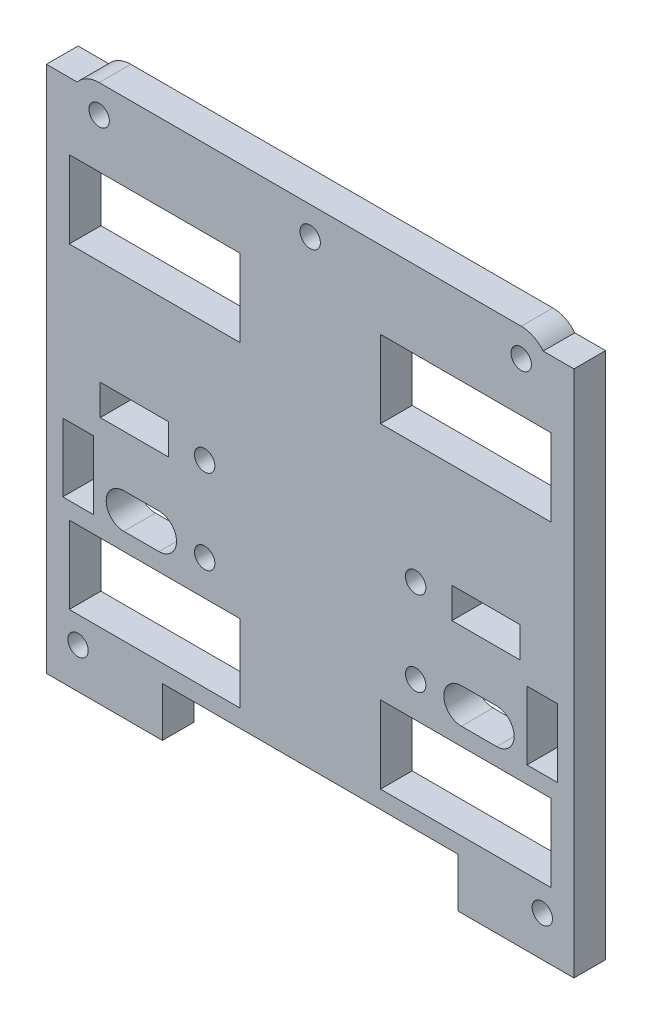
SolidWorks part; units mm, degrees
ref_plane "Front Plane" through (0, 0, 0) normal (0, 0, 1) x (1, 0, 0)
ref_plane "Top Plane" through (0, 0, 0) normal (0, 1, 0) x (1, 0, 0)
ref_plane "Right Plane" through (0, 0, 0) normal (1, 0, 0) x (0, 0, -1)
sketch "Sketch1" plane through (0, 0, 0) normal (0, 0, 1) x (1, 0, 0)
  line L0 (0, -37.5) -> (0, 37.5) construction
  line L1 (-47.5, -37.5) -> (47.5, -37.5)
  line L2 (-47.5, -37.5) -> (-47.5, 37.5)
  line L3 (-47.5, 37.5) -> (47.5, 37.5)
  line L4 (47.5, -37.5) -> (47.5, 37.5)
  line L5 (-47.5, -37.5) -> (47.5, 37.5) construction
  line L6 (-47.5, 37.5) -> (47.5, -37.5) construction
  line L7 (-47.5, 0) -> (47.5, 0) construction
  line L8 (-47.5, 22.5) -> (47.5, 22.5) construction
  line L9 (34.25, 17) -> (10, 28) construction
  line L10 (-34.25, 28) -> (-10, 28)
  line L11 (-34.25, 28) -> (-34.25, 17)
  line L12 (-34.25, 17) -> (-10, 17)
  line L13 (-10, 28) -> (-10, 17)
  line L14 (-34.25, 28) -> (-10, 17) construction
  line L15 (-34.25, 17) -> (-10, 28) construction
  line L16 (34.25, 28) -> (10, 17) construction
  line L17 (10, 28) -> (10, 17)
  line L18 (34.25, 17) -> (10, 17)
  line L19 (34.25, 28) -> (34.25, 17)
  line L20 (34.25, 28) -> (10, 28)
  line L21 (34.25, -28) -> (10, -17) construction
  line L22 (-34.25, -17) -> (-10, -28) construction
  line L23 (-34.25, -28) -> (-10, -17) construction
  line L24 (34.25, -17) -> (10, -28) construction
  line L25 (34.25, -28) -> (10, -28)
  line L26 (34.25, -28) -> (34.25, -17)
  line L27 (34.25, -17) -> (10, -17)
  line L28 (10, -28) -> (10, -17)
  line L29 (-10, -28) -> (-10, -17)
  line L30 (-34.25, -17) -> (-10, -17)
  line L31 (-34.25, -28) -> (-34.25, -17)
  line L32 (-34.25, -28) -> (-10, -28)
  point P0 (0, 0)
  point P12 (-22.125, 22.5)
  point P21 (22.125, 22.5)
  point P30 (22.125, -22.5)
  point P31 (-22.125, -22.5)
  dimension "D1" = 95
  dimension "D2" = 75
  dimension "D3" = 22.5
  dimension "D4" = 24.25
  dimension "D5" = 11
  dimension "D6" = 10
extrude "Boss-Extrude1" add sketch "Sketch1" along normal blind 4.5
sketch "Sketch8" plane through (0, 0, 4.5) normal (0, 0, 1) x (1, 0, 0)
  line L0 (-47.5, 37.5) -> (-47.5, -37.5) construction
  line L1 (47.5, -37.5) -> (47.5, 37.5) construction
  circle A0 centre (-47.5, 29.5) radius 8
  circle A1 centre (47.5, 29.5) radius 8
  dimension "D1" = 16
extrude "Boss-Extrude2" [suppressed] add sketch "Sketch8" against normal through all
sketch "Sketch2" plane through (0, 0, 4.5) normal (0, 0, 1) x (1, 0, 0)
  line L0 (0, -37.5) -> (0, 37.5) construction
  line L1 (-47.5, -37.5) -> (47.5, -37.5) construction
  line L2 (47.5, 37.5) -> (-47.5, 37.5) construction
  line L3 (-47.5, 0) -> (47.5, 0) construction
  line L4 (-47.5, 37.5) -> (-47.5, -37.5) construction
  line L5 (47.5, -37.5) -> (47.5, 37.5) construction
  line L6 (-40, 0) -> (40, 0) construction
  line L7 (-30, 35) -> (30, 35) construction
  circle A0 centre (-30, 35) radius 1.45
  circle A1 centre (30, 35) radius 1.45
  circle A2 centre (40, 0) radius 1.45
  circle A3 centre (-40, 0) radius 1.45
  circle A4 centre (0, 35) radius 1.45
  dimension "D1" = 2.9
  dimension "D7" = 2.9
  dimension "D8" = 2.9
  dimension "D9" = 2.9
  dimension "D2" = 30
  dimension "D3" = 35
  dimension "D4" = 80
  dimension "D5" = 40
  dimension "D6" = 0
extrude "screwHoles" cut sketch "Sketch2" against normal through all
sketch "Sketch3" plane through (0, 0, 4.5) normal (0, 0, 1) x (1, 0, 0)
  line L0 (-47.5, -20) -> (26.0486, -20) construction
  line L1 (-47.5, 37.5) -> (-47.5, -37.5) construction
  line L3 (0, 37.5) -> (0, -37.5) construction
  line L4 (47.5, 37.5) -> (-47.5, 37.5) construction
  line L5 (-47.5, -37.5) -> (47.5, -37.5) construction
  line L6 (18.95, -22.2) -> (9.05, -17.8) construction
  line L7 (-18.95, -17.8) -> (-9.05, -17.8)
  line L8 (-18.95, -17.8) -> (-18.95, -22.2)
  line L9 (-18.95, -22.2) -> (-9.05, -22.2)
  line L10 (-9.05, -17.8) -> (-9.05, -22.2)
  line L11 (-18.95, -17.8) -> (-9.05, -22.2) construction
  line L12 (-18.95, -22.2) -> (-9.05, -17.8) construction
  line L13 (18.95, -17.8) -> (9.05, -22.2) construction
  line L14 (9.05, -17.8) -> (9.05, -22.2)
  line L15 (18.95, -22.2) -> (9.05, -22.2)
  line L16 (18.95, -17.8) -> (18.95, -22.2)
  line L17 (18.95, -17.8) -> (9.05, -17.8)
  line L18 (-47.5, 37.5) -> (-47.5, -37.5) construction
  point P2 (-47.5, 0)
  point P12 (-14, -20)
  point P21 (14, -20)
  dimension "D1" = 9.9
  dimension "D3" = 14
  dimension "D4" = 20
extrude "BeltClamp" [suppressed] cut sketch "Sketch3" against normal through all
sketch "Sketch4" plane through (0, 0, 4.5) normal (0, 0, 1) x (1, 0, 0)
  line L0 (-47.5, 0) -> (47.5, 0) construction
  line L1 (-47.5, 37.5) -> (-47.5, -37.5) construction
  line L2 (47.5, -37.5) -> (47.5, 37.5) construction
  line L3 (0, 0) -> (0, 33.55) construction
  line L4 (-29.85, 2.175) -> (-20.15, 2.175)
  line L5 (-29.85, 2.175) -> (-29.85, -2.175)
  line L6 (-29.85, -2.175) -> (-20.15, -2.175)
  line L7 (-20.15, 2.175) -> (-20.15, -2.175)
  line L8 (-29.85, 2.175) -> (-20.15, -2.175) construction
  line L9 (-29.85, -2.175) -> (-20.15, 2.175) construction
  line L10 (29.85, -2.175) -> (20.15, 2.175) construction
  line L11 (29.85, 2.175) -> (20.15, -2.175) construction
  line L12 (20.15, 2.175) -> (20.15, -2.175)
  line L13 (29.85, -2.175) -> (20.15, -2.175)
  line L14 (29.85, 2.175) -> (29.85, -2.175)
  line L15 (29.85, 2.175) -> (20.15, 2.175)
  line L16 (-29.85, -2.175) -> (-20.15, 2.175) construction
  circle A0 centre (-40, 0) radius 1.45 construction
  circle A1 centre (0, 35) radius 1.45 construction
  point P6 (-25, 0)
  point P22 (25, 0)
  dimension "D3" = 0
  dimension "D2" = 4.35
  dimension "D4" = 25
extrude "Cut-Extrude3" cut sketch "Sketch4" against normal through all
sketch "Sketch5" plane through (0, 0, 4.5) normal (0, 0, 1) x (1, 0, 0)
  line L0 (-47.5, -9.75) -> (47.5, -9.75) construction
  line L1 (-47.5, 37.5) -> (-47.5, -37.5) construction
  line L2 (47.5, -37.5) -> (47.5, 37.5) construction
  line L4 (0, -37.5) -> (0, 37.5) construction
  line L5 (-47.5, -37.5) -> (47.5, -37.5) construction
  line L6 (47.5, 37.5) -> (-47.5, 37.5) construction
  line L7 (-30.825, -14.6) -> (-35.175, -4.9) construction
  line L8 (30.825, -4.9) -> (35.175, -4.9)
  line L9 (30.825, -4.9) -> (30.825, -14.6)
  line L10 (30.825, -14.6) -> (35.175, -14.6)
  line L11 (35.175, -4.9) -> (35.175, -14.6)
  line L12 (30.825, -4.9) -> (35.175, -14.6) construction
  line L13 (30.825, -14.6) -> (35.175, -4.9) construction
  line L14 (-30.825, -4.9) -> (-35.175, -14.6) construction
  line L15 (-35.175, -4.9) -> (-35.175, -14.6)
  line L16 (-30.825, -14.6) -> (-35.175, -14.6)
  line L17 (-30.825, -4.9) -> (-30.825, -14.6)
  line L18 (-30.825, -4.9) -> (-35.175, -4.9)
  line L19 (33, -9.75) -> (33, -37.5) construction
  line L20 (-33, -9.75) -> (-33, -37.5) construction
  line L21 (-33, -31.75) -> (33, -31.75) construction
  circle A0 centre (33, -31.75) radius 1.45
  circle A1 centre (-33, -31.75) radius 1.45
  point P15 (33, -9.75)
  point P24 (-33, -9.75)
  dimension "D5" = 2.9
  dimension "D2" = 9.7
  dimension "D3" = 4.35
  dimension "D4" = 33
  dimension "D6" = 22
  dimension "D1" = 9.75
extrude "Cut-Extrude4" cut sketch "Sketch5" against normal through all
sketch "Sketch9" plane through (0, 0, 4.5) normal (0, 0, 1) x (1, 0, 0)
  line L0 (47.5, 37.5) -> (-47.5, 37.5) construction
  line L1 (0, 37.5) -> (0, -37.5) construction
  line L2 (-47.5, -37.5) -> (47.5, -37.5) construction
  line L3 (50.5, 35) -> (45.5, 35) construction
  line L4 (-50.5, 35) -> (-45.5, 35) construction
  circle A0 centre (-30, 35) radius 4
  circle A1 centre (-30, 35) radius 1.45
  circle A2 centre (-30, 35) radius 1.45 construction
  circle A3 centre (30, 35) radius 1.45
  circle A4 centre (30, 35) radius 4
  point P17 (0, -37.5)
  dimension "D1" = 8
extrude "Boss-Extrude3" add sketch "Sketch9" against normal through all
sketch "Sketch10" plane through (0, 0, 4.5) normal (0, 0, 1) x (1, 0, 0)
  line L0 (-60, 37.5) -> (-37.5, 37.5)
  line L1 (-37.5, 37.5) -> (-37.5, -37.5)
  line L2 (-47.5, -37.5) -> (47.5, -37.5) construction
  line L3 (-37.5, -37.5) -> (-60, -37.5)
  line L4 (-60, -37.5) -> (-60, 37.5)
  line L5 (0, 37.5) -> (0, -37.5) construction
  line L6 (26.8775, 37.5) -> (-26.8775, 37.5) construction
  line L7 (60, -37.5) -> (60, 37.5)
  line L8 (37.5, -37.5) -> (60, -37.5)
  line L9 (37.5, 37.5) -> (37.5, -37.5)
  line L10 (60, 37.5) -> (37.5, 37.5)
  line L11 (-60, -37.5) -> (-60, 37.5)
  line L12 (-33.1225, 37.5) -> (-47.5, 37.5) construction
  line M3 (47.5, -37.5) -> (47.5, 37.5)
  line M7 (-47.5, 37.5) -> (-47.5, -37.5)
  line M8 (-47.5, -37.5) -> (47.5, -37.5)
  dimension "D3" = 0
  dimension "D1" = 75
  dimension "D2" = 60
extrude "Cut-Extrude5" cut sketch "Sketch10" against normal through all contours L1 L0 M7 M8 | L10 L9 M3 M8 region at (42.5, 0, 4.5) region at (-42.5, 0, 4.5)
sketch "Sketch11" plane through (0, 0, 4.5) normal (0, 0, 1) x (1, 0, 0)
  line L0 (-30, 39) -> (30, 39)
  line L1 (30, 39) -> (26.8775, 37.5)
  line L2 (26.8775, 37.5) -> (-26.8775, 37.5)
  line L3 (-26.8775, 37.5) -> (-30, 39)
  arc A0 (-26.8775, 37.5) -> (-33.1225, 37.5) centre (-30, 35) ccw construction
  arc A1 (33.1225, 37.5) -> (26.8775, 37.5) centre (30, 35) ccw construction
extrude "Boss-Extrude4" add sketch "Sketch11" against normal through all
sketch "Sketch12" plane through (0, 0, 4.5) normal (0, 0, 1) x (1, 0, 0)
  line L0 (-37.5, -12) -> (37.5, -12) construction
  line L1 (-37.5, 37.5) -> (-37.5, -37.5) construction
  line L2 (37.5, 37.5) -> (37.5, -37.5) construction
  line L3 (0, 0) -> (0, -37.5) construction
  line L4 (-37.5, -37.5) -> (37.5, -37.5) construction
  circle A0 centre (-15, -12) radius 1.45
  circle A1 centre (15, -12) radius 1.45
  dimension "D2" = 2.9
  dimension "D1" = 15
  dimension "D3" = 12
extrude "FanBraceScrews" cut sketch "Sketch12" against normal through all
sketch "Sketch13" plane through (0, 0, 4.5) normal (0, 0, 1) x (1, 0, 0)
  line L0 (-37.5, -37.5) -> (37.5, -37.5) construction
  line L1 (-21, -44.5) -> (21, -44.5)
  line L2 (-21, -44.5) -> (-21, -30.5)
  line L3 (-21, -30.5) -> (21, -30.5)
  line L4 (21, -44.5) -> (21, -30.5)
  line L5 (-21, -44.5) -> (21, -30.5) construction
  line L6 (-21, -30.5) -> (21, -44.5) construction
  point P0 (0, -37.5)
  dimension "D1" = 42
  dimension "D2" = 7
extrude "Cut-Extrude7" cut sketch "Sketch13" against normal through all
sketch "Sketch20" plane through (0, 0, 0) normal (0, 0, -1) x (-1, 0, 0)
  line L0 (15, -10.55) -> (15, 0) construction
  line L1 (0, 0) -> (0, 8.2059) construction
  line L2 (-15, -10.55) -> (-15, 0) construction
  circle A0 centre (15, -12) radius 1.45 construction
  circle A1 centre (15, 0) radius 1.45
  circle A2 centre (-15, 0) radius 1.45
  dimension "D1" = 12
extrude "Cut-Extrude11" cut sketch "Sketch20" against normal through all
sketch "Sketch14" plane through (0, 0, 4.5) normal (0, 0, 1) x (1, 0, 0)
  line L0 (15, -13.45) -> (15, 0) construction
  line L1 (0, 0) -> (0, -40.3958) construction
  line L2 (-15, -13.45) -> (-15, 0) construction
  circle A0 centre (15, -12) radius 1.45 construction
  circle A1 centre (15, 0) radius 1.45
  circle A2 centre (-15, 0) radius 1.45
  dimension "D2" = 2.9
  dimension "D1" = 12
extrude "Cut-Extrude8" [suppressed] cut sketch "Sketch14" against normal through all
sketch "Sketch15" plane through (0, 0, 4.5) normal (0, 0, 1) x (1, 0, 0)
  line L0 (-25, 1.5) -> (-25, -10.5) construction
  line L2 (0, 0) -> (0, -11.0705) construction
  line L3 (16, -8.3509) -> (25, -10.5) construction
  line L4 (25, 1.5) -> (25, -10.5) construction
  circle A0 centre (-25, 1.5) radius 1.45
  circle A1 centre (-25, -10.5) radius 1.45
  circle A2 centre (25, -10.5) radius 1.45
  circle A3 centre (25, 1.5) radius 1.45
  circle A5 centre (-15, -12) radius 1.45 construction
  dimension "D1" = 12
  dimension "D3" = 2.9
  dimension "D4" = 2.9
  dimension "D2" = 25
  dimension "D5" = 1.5
extrude "BeltClipScrews" [suppressed] cut sketch "Sketch15" against normal through all
sketch "Sketch16" [suppressed] plane through (0, 0, 4.5) normal (0, 0, 1) x (1, 0, 0)
  line L0 (0, 0) -> (0, -11.3016) construction
  line L1 (-29.85, 2.175) -> (-20.15, 2.175)
  line L2 (-29.85, 2.175) -> (-29.85, -2.175)
  line L3 (-29.85, -2.175) -> (-20.15, -2.175)
  line L4 (-20.15, 2.175) -> (-20.15, -2.175)
  line L5 (-35.175, -4.9) -> (-30.825, -4.9)
  line L6 (-35.175, -4.9) -> (-35.175, -14.6)
  line L7 (-35.175, -14.6) -> (-30.825, -14.6)
  line L8 (-30.825, -4.9) -> (-30.825, -14.6)
  line L9 (30.825, -4.9) -> (30.825, -14.6)
  line L10 (35.175, -14.6) -> (30.825, -14.6)
  line L11 (35.175, -4.9) -> (35.175, -14.6)
  line L12 (35.175, -4.9) -> (30.825, -4.9)
  line L13 (20.15, 2.175) -> (20.15, -2.175)
  line L14 (29.85, -2.175) -> (20.15, -2.175)
  line L15 (29.85, 2.175) -> (29.85, -2.175)
  line L16 (29.85, 2.175) -> (20.15, 2.175)
  line L17 (-30.825, -4.9) -> (-30.825, -14.6)
extrude "Boss-Extrude5" [suppressed] add sketch "Sketch16" against normal through all contours L8 L5 L6 L7 | L4 L1 L2 L3 | L15 L16 L13 L14 | L11 L12 L9 L10
sketch "Sketch17" plane through (0, 0, 4.5) normal (0, 0, 1) x (1, 0, 0)
  line L0 (0, -30.5) -> (0, 0) construction
  line L1 (21, -30.5) -> (-21, -30.5) construction
  line L2 (-37.5, -37.5) -> (-46.5, -37.5)
  line L3 (-46.5, -37.5) -> (-46.5, -22.5)
  line L4 (-46.5, -22.5) -> (-43.5, -22.5)
  line L5 (-43.5, -22.5) -> (-43.5, -32.5)
  line L6 (-43.5, -32.5) -> (-37.5, -32.5)
  line L7 (-37.5, 37.5) -> (-37.5, -37.5) construction
  line L8 (-37.5, -32.5) -> (-37.5, -37.5)
  line L9 (-37.5, -37.5) -> (-37.5303, -37.4889)
  dimension "D1" = 3
  dimension "D2" = 6
  dimension "D3" = 5
  dimension "D4" = 15
extrude "Boss-Extrude6" [suppressed] add sketch "Sketch17" against normal through all contours L8 L6 L5 L4 L3 L2
sketch "Sketch18" [suppressed] plane through (0, 0, 0) normal (0, 0, 1) x (1, 0, 0)
  line L0 (0, -30.5) -> (0, 0) construction
  line L1 (-37.5, -37.5) -> (-21, -37.5) construction
  line L7 (-37.5, -27.5) -> (-37.5, -22.5)
  line L9 (-43.5, -27.5) -> (-37.5, -27.5)
  line L10 (-37.5, -30) -> (-45.5, -30) construction
  line L11 (-37.5, 37.5) -> (-37.5, -37.5) construction
  line L12 (-43.5, -37.5) -> (-43.5, -27.5)
  line L13 (-46.5, -37.5) -> (-43.5, -37.5)
  line L14 (-46.5, -22.5) -> (-46.5, -37.5)
  line L15 (-37.5, -22.5) -> (-46.5, -22.5)
  dimension "D1" = 6
  dimension "D2" = 15
  dimension "D3" = 5
extrude "Boss-Extrude7" [suppressed] add sketch "Sketch18" along normal through all
mirror "Mirror1" [suppressed] about plane through (0, 0, 0) normal (1, 0, 0)
fillet "Fillet1" [suppressed] radius 2
mirror "Mirror2" [suppressed] about plane through (0, 0, 0) normal (1, 0, 0)
fillet "Fillet2" [suppressed] radius 2
sketch "Sketch19" plane through (0, 0, 4.5) normal (0, 0, 1) x (1, 0, 0)
  line L0 (21.5, -12) -> (26.5, -12) construction
  line L1 (21.5, -9.5) -> (26.5, -9.5)
  line L2 (21.5, -14.5) -> (26.5, -14.5)
  line L3 (0, 0) -> (0, -15.8058) construction
  line L4 (-21.5, -12) -> (-26.5, -12) construction
  line L5 (-21.5, -9.5) -> (-26.5, -9.5)
  line L6 (-21.5, -14.5) -> (-26.5, -14.5)
  arc A0 (21.5, -9.5) -> (21.5, -14.5) centre (21.5, -12) ccw
  arc A1 (26.5, -14.5) -> (26.5, -9.5) centre (26.5, -12) ccw
  arc A2 (-21.5, -9.5) -> (-21.5, -14.5) centre (-21.5, -12) cw
  arc A3 (-26.5, -14.5) -> (-26.5, -9.5) centre (-26.5, -12) cw
  point P2 (24, -12)
  point P13 (-24, -12)
  dimension "D1" = 5
  dimension "D2" = 5
  dimension "D3" = 24
  dimension "D4" = 12
extrude "Cut-Extrude9" cut sketch "Sketch19" against normal through all
sketch "Sketch21" [suppressed] plane through (0, 0, 0) normal (0, 0, -1) x (-1, 0, 0)
  line L0 (0, 0) -> (0, -30.5) construction
  line L1 (-21, -30.5) -> (21, -30.5) construction
  circle A0 centre (-33, -31.75) radius 1.45
  circle A1 centre (33, -31.75) radius 1.45
  dimension "D1" = 2.9
  dimension "D2" = 33
  dimension "D3" = 31.75
extrude "Cut-Extrude12" [suppressed] cut sketch "Sketch21" against normal through all
equation "\"X-ROD-SPACING\"=45"
equation "\"Y-ROD-SPACING\"=75"
equation "\"Z-ROD-SPACING\"=17.5"
equation "\"Y-BED-OFFSET\"=2"
equation "\"Y-BED-ROD-INSET\"=3.5"
equation "\"Y-BED-SCREW-SPACING\"=209"
equation "\"Y-BED-SCREW-CUTOUT-SLOT-HEIGHT\"=2"
equation "\"T-SLOT-NUT-FILLET-RADIUS\"=0.5"
equation "\"T-SLOT-SCREW-SHAFT-RADIUS\"=1.55"
equation "\"T-SLOT-SCREW-SHAFT-CUTOUT-LENGTH\"=11"
equation "\"T-SLOT-NUT-DEPTH\"=3.5"
equation "\"T-SLOT-NUT-WIDTH\"=2.85"
equation "\"T-SLOT-NUT-END-DISTANCE\"=8"
equation "\"ACRYLIC-THICKNESS\"=10"
equation "\"ACRYLIC-THICKNESS2\"=4.5"
equation "\"ACRYLIC-TAB-CUTOUT-SIZE\"=\"ACRYLIC-THICKNESS\"+\"ACRYLIC-TAB-TOLERANCE\"*2"
equation "\"ACRYLIC-TAB-WIDTH\"=\"ACRYLIC-THICKNESS\""
equation "\"ACRYLIC-M3-HOLE\"=2.9"
equation "\"SMOOTHROD-CAP-SCREW-DISTANCE\"=20"
equation "\"FRAME-WIDTH-INNER\"=370"
equation "\"NEMA17-HOLE-SPACING\"=31"
equation "\"NEMA17-CENTRAL-CUTOUT\"=22.5"
equation "\"Z-BRACKET-REACH\"=57"
equation "\"Z-ROD-INSET\"=13.5"
equation "\"TOP-BRACKET-SPACING\"=40"
equation "\"SMOOTHROD-X-LENGTH\"=350"
equation "\"SMOOTHROD-Y-LENGTH\"=350"
equation "\"SMOOTHROD-Z-LENGTH\"=350"
equation "\"SMOOTHROD-TIGHTENING-HEADROOM\"=.25"
equation "\"LEADSCREW-Z-LENGTH\"=300"
equation "\"SCREW-LENGTH-FRAME\"=\"ACRYLIC-THICKNESS\" + 10"
equation "\"SCREW-LENGTH-MOTOR\"=\"ACRYLIC-THICKNESS\" + 5"
equation "\"SCREW-HEAD-RADIUS\"=6"
equation "\"PRINTED-X-SMOOTHROD-DIAMETER\"=8.8"
equation "\"PRINTED-X-SMOOTHROD-CUTOUT\"=10"
equation "\"PRINTED-X-BASE-HEIGHT\"=10"
equation "\"PRINTED-LM8UU-CUTOUT-SIZE\"=15.5"
equation "\"PRINTED-LM8UU-CUTOUT-LENGTH\"=24.5"
equation "\"PRINTED-X-IDLER-HEIGHT\"=16"
equation "\"PSU-MOUNTING-WIDTH\"=95"
equation "\"PSU-MOUNTING-HEIGHT\"=177"
equation "\"Y-BELT-TO-ROD-DISTANCE\"=20"
equation "\"SPOOL-HOLDER-ROD-SPACING\"=150"
equation "\"D3@Sketch1\"=\"X-ROD-SPACING\"/2"
equation "\"D4@Sketch1\"=\"ACRYLIC-X-CARRIAGE-LM8UU-CUTOUT-WIDTH\""
equation "\"D1@Boss-Extrude1\"=\"ACRYLIC-THICKNESS2\""
equation "\"D1@Sketch2\"=\"ACRYLIC-M3-HOLE\""
equation "\"D1@Sketch3\"=\"ACRYLIC-TAB-CUTOUT-SIZE\""
equation "\"D2@Sketch3\"=\"ACRYLIC-THICKNESS2\"+\"ACRYLIC-TAB-TOLERANCE\"*2"
equation "\"ACRYLIC-X-CARRIAGE-WIDTH\"=55"
equation "\"ACRYLIC-X-CARRIAGE-HEIGHT\"=75"
equation "\"D2@Sketch1\"=\"ACRYLIC-X-CARRIAGE-HEIGHT\""
equation "\"ACRYLIC-X-CARRIAGE-CENTER-TAB-SPACING\"=14"
equation "\"D3@Sketch3\"=\"ACRYLIC-X-CARRIAGE-CENTER-TAB-SPACING\""
equation "\"SCREW-LENGTH-EXTRUDER\"=28"
equation "\"ACRYLIC-X-CARRIAGE-SCREW-SPACING-X\"=15"
equation "\"ACRYLIC-X-CARRIAGE-SCREW-SPACING-Y\"=33"
equation "\"D1@Sketch4\"=\"ACRYLIC-TAB-WIDTH\"-\"KERF\"*4"
equation "\"D2@Sketch4\"=\"ACRYLIC-THICKNESS2\"-\"KERF\"*2"
equation "\"D2@Sketch5\"=\"ACRYLIC-TAB-WIDTH\"-\"KERF\"*4"
equation "\"D3@Sketch5\"=\"ACRYLIC-THICKNESS2\"-\"KERF\"*2"
equation "\"ACRYLIC-X-CARRIAGE-EXTRUDER-SHELF-DEPTH\"=\"ACRYLIC-X-CARRIAGE-EXTRUDER-OFFSET\" + 28"
equation "\"ACRYLIC-X-CARRIAGE-EXTRUDER-BRACE-SPACING\"=23"
equation "\"D4@Sketch5\"=\"ACRYLIC-X-CARRIAGE-DUAL-MOUNT-BRACE-WIDTH\""
equation "\"D1@Sketch5\"=\"ACRYLIC-THICKNESS2\"/2 + 7.5"
equation "\"D4@Sketch2\"=\"ACRYLIC-X-CARRIAGE-DUAL-MOUNT-SCREW-WIDTH\"*2"
equation "\"D5@Sketch2\"=\"ACRYLIC-X-CARRIAGE-DUAL-MOUNT-SCREW-WIDTH\""
equation "\"D7@Sketch2\"=\"ACRYLIC-M3-HOLE\""
equation "\"D8@Sketch2\"=\"ACRYLIC-M3-HOLE\""
equation "\"ACRYLIC-X-CARRIAGE-LM8UU-CUTOUT-WIDTH\"=24.25"
equation "\"ACRYLIC-TAB-TOLERANCE\"=-.05"
equation "\"ACRYLIC-X-CARRIAGE-EXTRUDER-OFFSET\"=26"
equation "\"ACRYLIC-X-CARRIAGE-EXTRUDER-ANGLE\"=90"
equation "\"ACRYLIC-X-CARRIAGE-EXTRUDER-BRACE-TAB-OFFSET\"=20"
equation "\"ACRYLIC-X-CARRIAGE-EXTRUDER-BRACE-HEIGHT\"=35"
equation "\"ACRYLIC-X-CARRIAGE-EXTRUDER-BRACE-SCREW-SPACING\"=22"
equation "\"D5@Sketch5\"=\"ACRYLIC-M3-HOLE\""
equation "\"ACRYLIC-X-CARRIAGE-DUAL-WIDTH-MULTIPLIER\"=1.65"
equation "\"ACRYLIC-X-CARRIAGE-DUAL-HOTEND-SPACING\"=42"
equation "\"ACRYLIC-X-CARRIAGE-DUAL-WIDTH\"=75"
equation "\"ACRYLIC-X-CARRIAGE-DUAL-HOTEND-SEPARATION\"=36"
equation "\"ACRYLIC-X-CARRIAGE-DUAL-MOUNT-PLATE-DEPTH\"=75"
equation "\"ACRYLIC-X-CARRIAGE-DUAL-MOUNT-BRACE-WIDTH\"=33"
equation "\"ACRYLIC-X-CARRIAGE-DUAL-MOUNT-SCREW-WIDTH\"=40"
equation "\"D9@Sketch2\"=\"ACRYLIC-M3-HOLE\""
equation "\"ACRYLIC-X-CARRIAGE-LM8UU-CUTOUT-HEIGHT\"=11.0"
equation "\"D5@Sketch1\"=\"ACRYLIC-X-CARRIAGE-LM8UU-CUTOUT-HEIGHT\""
equation "\"D1@Sketch10\"=\"ACRYLIC-X-CARRIAGE-DUAL-WIDTH\""
equation "\"D2@Sketch12\"=\"ACRYLIC-M3-HOLE\""
equation "\"D2@Sketch14\"=\"ACRYLIC-M3-HOLE\""
equation "\"D3@Sketch15\"=\"ACRYLIC-M3-HOLE\""
equation "\"D4@Sketch15\"=\"ACRYLIC-M3-HOLE\""
equation "\"KERF\"=0.075"
equation "\"ACRYLIC-THICKNESS-TAB-CUTOUT-WIDTH\"=\"ACRYLIC-THICKNESS\"-\"KERF\"*2"
equation "\"ACRYLIC-THICKNESS-TAB-CUTOUT-HEIGHT\"=\"ACRYLIC-TAB-WIDTH\"-\"KERF\"*4"
equation "\"ACRYLIC-THICKNESS2-TAB-CUTOUT-WIDTH\"=\"ACRYLIC-THICKNESS2\"-\"KERF\"*2"
equation "\"ACRYLIC-THICKNESS2-TAB-CUTOUT-HEIGHT\"=\"ACRYLIC-TAB-WIDTH\"-\"KERF\"*4"
equation "\"PRINTED-M3-HOLE\"=3.5"
equation "\"PRINTED-M3-NUT-AF\"=6.25"
equation "\"ACRYLIC-X-CARRIAGE-DUAL-FAN-OFFSET\"=52"
equation "\"ACRYLIC-X-CARRIAGE-DUAL-FAN-HEIGHT\"=20"
equation "\"BLOWER-FAN-WIDTH\"=15"
equation "\"D1@Sketch21\"=\"ACRYLIC-M3-HOLE\""
equation "\"D2@Sketch21\"=\"ACRYLIC-X-CARRIAGE-DUAL-MOUNT-BRACE-WIDTH\""
equation "\"D3@Sketch21\"=\"ACRYLIC-THICKNESS2\"/2 + 7.5+22"
